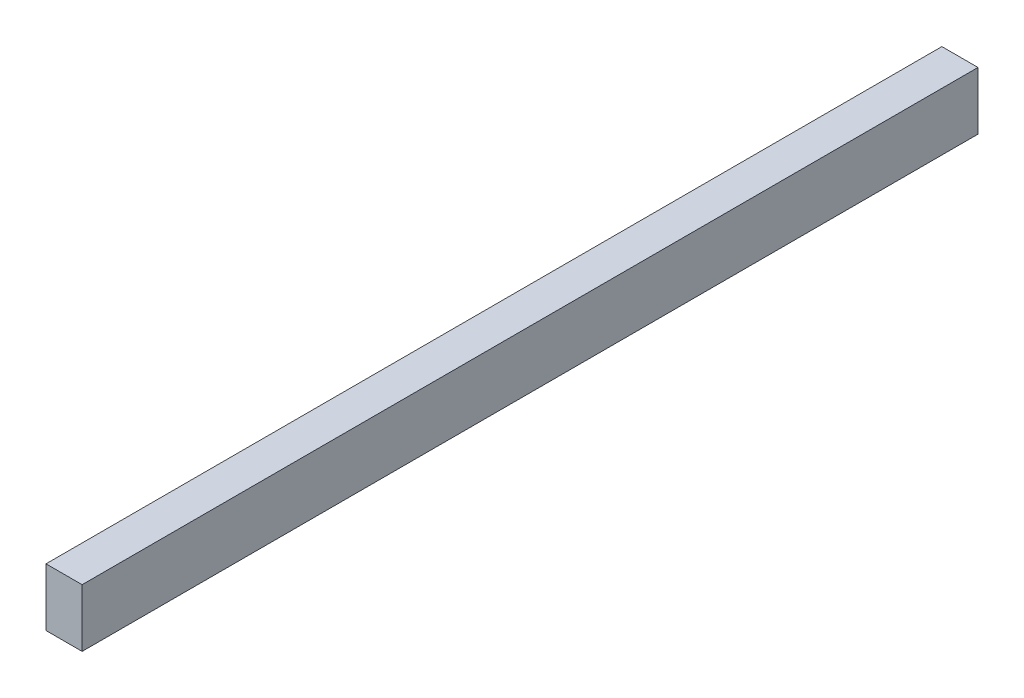
SolidWorks part; units mm, degrees
ref_plane "Plan de face" through (0, 0, 0) normal (0, 0, 1) x (1, 0, 0)
ref_plane "Plan de dessus" through (0, 0, 0) normal (0, 1, 0) x (1, 0, 0)
ref_plane "Plan de droite" through (0, 0, 0) normal (1, 0, 0) x (0, 0, -1)
sketch "Esquisse1" plane through (0, 0, 0) normal (0, 0, 1) x (1, 0, 0)
  line L1 (0, 0) -> (25, 0)
  line L2 (0, 0) -> (0, 40)
  line L3 (0, 40) -> (25, 40)
  line L4 (25, 0) -> (25, 40)
  dimension "D1" = 25
  dimension "D2" = 40
extrude "Boss.-Extru.1" add sketch "Esquisse1" along normal blind 620
